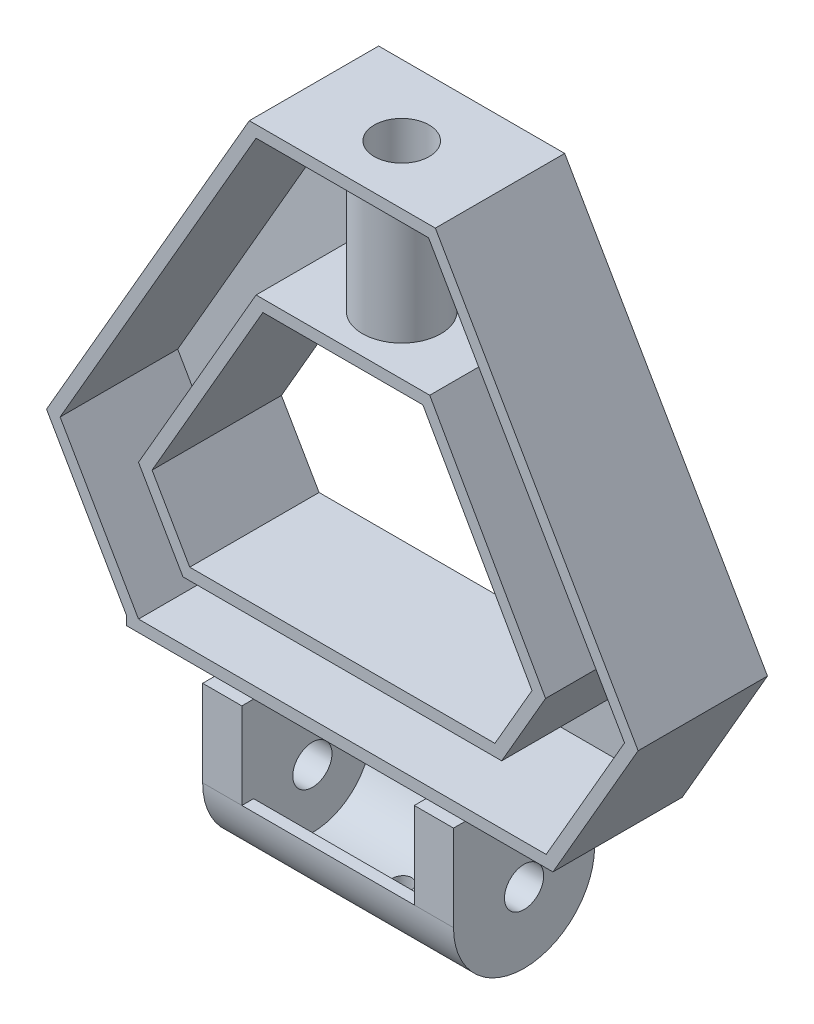
SolidWorks part; units mm, degrees
ref_plane "Alzado" through (0, 0, 0) normal (0, 0, 1) x (1, 0, 0)
ref_plane "Planta" through (0, 0, 0) normal (0, 1, 0) x (1, 0, 0)
ref_plane "Vista lateral" through (0, 0, 0) normal (1, 0, 0) x (0, 0, -1)
sketch "Croquis2" plane through (0, 0, 0) normal (1, 0, 0) x (0, 0, -1)
  line L0 (15, 0) -> (15, 200)
  line L1 (-15, 0) -> (-15, 200)
  line L2 (-15, 200) -> (15, 200) construction
  circle A0 centre (0, 0) radius 5
  arc A1 (-15, 0) -> (15, 0) centre (0, 0) ccw
  arc A2 (15, 200) -> (-15, 200) centre (0, 200) ccw
  circle A3 centre (0, 200) radius 5
extrude "Saliente-Extruir2" add sketch "Croquis2" along normal blind 64
sketch "Croquis3" plane through (64, 0, 0) normal (1, 0, 0) x (0, 0, -1)
  line L0 (15, 0) -> (15, 25)
  line L1 (15, 0) -> (15, 200) construction
  line L2 (15, 25) -> (-15, 25)
  line L3 (-15, 200) -> (-15, 0) construction
  line L4 (-15, 25) -> (-15, 0)
  circle A0 centre (0, 0) radius 5
  arc A1 (-15, 0) -> (15, 0) centre (0, 0) ccw
extrude "Saliente-Extruir3" add sketch "Croquis3" along normal blind 20
ref_plane "Plano1" through (32, 0, 0) normal (-1, 0, 0) x (0, 0, 1)
mirror "Simetría1" about plane through (32, 0, 0) normal (-1, 0, 0) of "Saliente-Extruir3"
sketch "Croquis5" plane through (64, 0, 0) normal (1, 0, 0) x (0, 0, -1)
  line L1 (-15, 25) -> (15, 25)
  line L2 (-15, 25) -> (-15, 217.8759)
  line L3 (-15, 217.8759) -> (15, 217.8759)
  line L4 (15, 25) -> (15, 217.8759)
extrude "Cortar-Extruir2" cut sketch "Croquis5" against normal blind 91
sketch "Croquis6" plane through (0, 0, 15) normal (0, 0, 1) x (1, 0, 0)
  line L0 (84, 25) -> (103.9988, 59.639)
  line L1 (84, 25) -> (-20, 25) construction
  line L2 (-20, 25) -> (-40, 59.641)
  line L3 (-40, 59.641) -> (10, 146.2436)
  line L4 (103.9988, 59.639) -> (53.9976, 146.2436)
  line L5 (10, 146.2436) -> (53.9976, 146.2436)
  line L6 (-20, 25) -> (84, 25)
  line L7 (-8.6603, 40) -> (-20, 59.641)
  line L8 (-20, 59.641) -> (10, 111.6025)
  line L9 (10, 111.6025) -> (54.3, 111.6025)
  line L10 (54.3, 111.6025) -> (83.8462, 59.3816)
  line L11 (72.6585, 40) -> (83.8462, 59.3816)
  line L13 (32, 40) -> (72.6585, 40)
  line L14 (32, 40) -> (-8.6603, 40)
  point P13 (69.0731, 85.4921)
  dimension "D1" = 120
  dimension "D2" = 120
  dimension "D3" = 120
  dimension "D4" = 120
  dimension "D5" = 44.3
  dimension "D6" = 180
  dimension "D7" = 17.32
extrude "Saliente-Extruir4" add sketch "Croquis6" against normal blind 30
sketch "Croquis7" plane through (0, 111.6025, 0) normal (0, -1, 0) x (1, 0, 0)
  line L0 (32.15, 15) -> (32.15, 0) construction
  line L1 (54.3, 15) -> (10, 15) construction
  circle A0 centre (32.15, 0) radius 10
extrude "Cortar-Extruir3" cut sketch "Croquis7" against normal up to surface (34.641 mm away) up to face at (31.9988, 146.2436, 0)
sketch "Croquis10" plane through (0, 0, 15) normal (0, 0, 1) x (1, 0, 0)
  line L1 (38.0431, -37.5344) -> (84, -37.5344)
  line L2 (38.0431, -37.5344) -> (38.0431, 25)
  line L3 (38.0431, 25) -> (84, 25)
  line L4 (84, -37.5344) -> (84, 25)
  line L5 (-25.9569, -37.5344) -> (-20, -37.5344)
  line L6 (-25.9569, -37.5344) -> (-25.9569, 25)
  line L7 (-25.9569, 25) -> (-20, 25)
  line L8 (-20, -37.5344) -> (-20, 25)
extrude "Cortar-Extruir6" cut sketch "Croquis10" against normal blind 45
shell "Vaciado1" thickness 3 removed face at (27.5647, 54.0852, 15) outward yes
sketch "Croquis12" plane through (41.0431, 0, 0) normal (1, 0, 0) x (0, 0, -1)
  circle A0 centre (0, 0) radius 5
extrude "Cortar-Extruir7" cut sketch "Croquis12" against normal blind 73
sketch "Croquis13" plane through (0, 0, 0) normal (0, 1, 0) x (1, 0, 0)
  line L0 (41.0431, 0) -> (32.15, 0)
  line L1 (41.0431, -18) -> (41.0431, 18) construction
  circle A0 centre (32.15, 0) radius 2.5
extrude "Cortar-Extruir8" cut sketch "Croquis13" against normal blind 40 contours A0 region at (29.7207, 0, 0)
sketch "Croquis14" plane through (41.0431, 0, 0) normal (1, 0, 0) x (0, 0, -1)
  line L0 (18, 22) -> (18, 0) construction
  line L5 (-15, 0) -> (-18, 0)
  line L6 (18, 0) -> (15, 0)
  arc A0 (-18, 0) -> (18, 0) centre (0, 0) ccw construction
  arc A2 (-18, 0) -> (18, 0) centre (0, 0) ccw
  arc A3 (-15, 0) -> (15, 0) centre (0, 0) ccw
extrude "Saliente-Extruir8" add sketch "Croquis14" along normal up to vertex (44.689 mm away) up to point (85.7321, 22, 15)
sketch "Croquis17" plane through (41.0431, 0, 0) normal (1, 0, 0) x (0, 0, -1)
  line L1 (-15, 22) -> (15, 22)
  line L2 (-15, 22) -> (-15, 0)
  line L4 (15, 22) -> (15, 0)
  arc A0 (-15, 0) -> (15, 0) centre (0, 0) ccw
extrude "Cortar-Extruir10" cut sketch "Croquis17" against normal blind 21
sketch "Croquis18" plane through (38.0431, 0, 0) normal (-1, 0, 0) x (0, 0, 1)
  line L1 (-15, 25) -> (15, 25)
  line L2 (-15, 25) -> (-15, 22)
  line L3 (-15, 22) -> (15, 22)
  line L4 (15, 25) -> (15, 22)
extrude "Saliente-Extruir9" add sketch "Croquis18" along normal up to surface (58.0431 mm away) up to face at (-20, 0, 5)
sketch "Croquis19" plane through (41.0431, 0, 0) normal (1, 0, 0) x (0, 0, -1)
  line L1 (15, 0) -> (18, 0)
  line L2 (15, 0) -> (15, 22)
  line L3 (15, 22) -> (18, 22)
  line L4 (18, 0) -> (18, 22)
extrude "Saliente-Extruir10" add sketch "Croquis19" along normal up to surface (44.689 mm away) up to face at (85.7321, -8.25, 0)
sketch "Croquis21" plane through (85.7321, 0, 0) normal (1, 0, 0) x (0, 0, -1)
  line L1 (-15, 22) -> (15, 22)
  line L2 (-15, 22) -> (-15, 0)
  line L4 (15, 22) -> (15, 0)
  circle A0 centre (0, 0) radius 5
  arc A1 (-15, 0) -> (15, 0) centre (0, 0) ccw
extrude "Saliente-Extruir11" add sketch "Croquis21" against normal blind 3 contours L4 L1 L2 A1 | A0
sketch "Croquis22" plane through (0, 0, 15) normal (0, 0, 1) x (1, 0, 0)
  line L0 (31.366, 22) -> (63.366, 22)
  line L1 (82.7321, 22) -> (-20, 22) construction
  line L2 (31.366, 22) -> (-0.634, 22)
  line L3 (-0.634, 22) -> (-0.634, 0)
  line L4 (85.7321, 0) -> (-23, 0) construction
  line L5 (-0.634, 0) -> (63.366, 0)
  line L6 (63.366, 0) -> (63.366, 22)
  line L8 (63.366, 0) -> (-0.634, 0)
  line L9 (63.366, 0) -> (63.366, -20.5107)
  line L10 (63.366, -20.5107) -> (-0.634, -20.5107)
  line L11 (-0.634, 0) -> (-0.634, -20.5107)
  line L13 (63.366, 22) -> (63.366, -18)
  line L16 (-0.634, 22) -> (-25.7493, 22)
  line L17 (-0.634, 22) -> (-0.634, -21.8329)
  line L18 (-0.634, -21.8329) -> (-25.7493, -21.8329)
  line L19 (-25.7493, 22) -> (-25.7493, -21.8329)
  line L20 (63.366, 22) -> (86.7799, 22)
  line L21 (63.366, 22) -> (63.366, -20.5107)
  line L22 (63.366, -20.5107) -> (86.7799, -20.5107)
  line L23 (86.7799, 22) -> (86.7799, -20.5107)
  line M2 (-20, 0) -> (-20, 22)
  line M3 (-20, 22) -> (82.7321, 22)
  line M4 (82.7321, 22) -> (82.7321, 0)
  line M5 (82.7321, 0) -> (85.7321, 0)
  line M6 (85.7321, 0) -> (85.7321, 22)
  line M12 (-23, 24.1962) -> (-23, 0)
  line M13 (-23, 0) -> (-20, 0)
extrude "Cortar-Extruir12" cut sketch "Croquis22" against normal blind 65 and the other way blind 65 contours L23 L20 L6 L9 L22 M6 M5 M4 M3 | L16 L19 L18 L17 L11 L3 M3 M2 M13 M12 region at (74.4225, 0.0163, 15) region at (-12.6618, -0.6127, 15)
sketch "Croquis23" plane through (0, 0, 15) normal (0, 0, 1) x (1, 0, 0)
  line L0 (-23, 24.1962) -> (-23, 0) construction
  line L1 (-20, 0) -> (-23, 0)
  line L2 (-20, 0) -> (-20, 22)
  line L3 (-20, 22) -> (-23, 22)
  line L4 (-23, 0) -> (-23, 22)
  line L6 (82.7321, 22) -> (85.7321, 22)
  line L7 (82.7321, 22) -> (82.7321, 0)
  line L8 (82.7321, 0) -> (85.7321, 0)
  line L9 (85.7321, 22) -> (85.7321, 0)
extrude "Cortar-Extruir13" cut sketch "Croquis23" against normal blind 65
sketch "Croquis24" plane through (63.366, 0, 0) normal (1, 0, 0) x (0, 0, -1)
  line L1 (18, 22) -> (-18, 22)
  line L2 (18, 22) -> (18, 0)
  line L3 (18, 0) -> (15, 0)
  line L4 (-18, 22) -> (-18, 0)
  line L5 (-15, 0) -> (-18, 0)
  arc A0 (-15, 0) -> (15, 0) centre (0, 0) ccw
  circle A1 centre (0, 0) radius 5
  arc A2 (-18, 0) -> (18, 0) centre (0, 0) ccw
  line M9 (15, 22) -> (15, 0)
  arc M10 (15, 0) -> (-15, 0) centre (0, 0) cw
  line M11 (-15, 0) -> (-18, 0)
  arc M12 (-18, 0) -> (18, 0) centre (0, 0) ccw
extrude "Saliente-Extruir12" add sketch "Croquis24" against normal blind 10 contours L1 L4 A1 M11 M10 M9 | L3 M12 M10 M11 region at (63.366, 5.7309, 1.088) region at (63.366, -17.5975, 0)
sketch "Croquis25" plane through (-0.634, 0, 0) normal (-1, 0, 0) x (0, 0, 1)
  line L0 (15, 0) -> (18, 0)
  line L1 (-18, 22) -> (18, 22)
  line L2 (-18, 22) -> (-18, 0)
  line L3 (-18, 0) -> (-15, 0)
  line L4 (18, 22) -> (18, 0)
  arc A0 (-18, 0) -> (18, 0) centre (0, 0) ccw
  arc A1 (-15, 0) -> (15, 0) centre (0, 0) ccw
  circle A2 centre (0, 0) radius 5
  arc M6 (-18, 0) -> (18, 0) centre (0, 0) ccw
  line M7 (18, 0) -> (15, 0)
  arc M8 (15, 0) -> (-15, 0) centre (0, 0) cw
  line M9 (-15, 0) -> (-15, 22)
extrude "Saliente-Extruir13" add sketch "Croquis25" against normal blind 10 contours L4 L1 A2 M9 M8 M7 | L3 M6 M7 M8 region at (-0.634, 5.7309, 1.088) region at (-0.634, -0.4025, 16.5)
